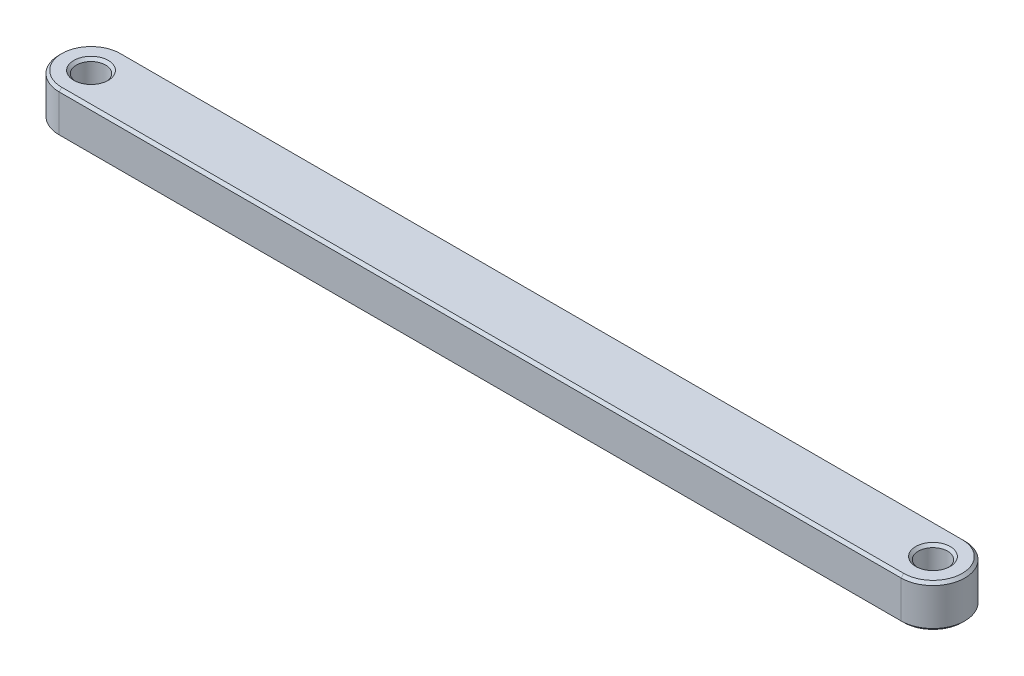
SolidWorks part; units mm, degrees
ref_plane "Front Plane" through (0, 0, 0) normal (0, 0, 1) x (1, 0, 0)
ref_plane "Top Plane" through (0, 0, 0) normal (0, 1, 0) x (1, 0, 0)
ref_plane "Right Plane" through (0, 0, 0) normal (1, 0, 0) x (0, 0, -1)
sketch "Sketch1" plane through (0, 0, 0) normal (0, 1, 0) x (1, 0, 0)
  line L0 (0, 0) -> (125.7224, 0) construction
  line L1 (0, 4.7625) -> (125.7224, 4.7625)
  line L2 (0, -4.7625) -> (125.7224, -4.7625)
  arc A0 (0, 4.7625) -> (0, -4.7625) centre (0, 0) ccw
  arc A1 (125.7224, -4.7625) -> (125.7224, 4.7625) centre (125.7224, 0) ccw
  circle A2 centre (0, 0) radius 2.1828
  circle A3 centre (125.7224, 0) radius 2.1828
  point P3 (62.8612, 0)
  dimension "D2" = 4.7625
  dimension "D3" = 4.3656
  dimension "D4" = 4.3656
  dimension "D1" = 125.7224
extrude "Boss-Extrude1" add sketch "Sketch1" along normal blind 6.35
chamfer "Chamfer1" distance 0.3969 angle 45 12 edges at (125.7224, 0, 2.1828) (0, 0, 2.1828) (62.8612, 0, 4.7625) (130.4849, 0, 0) (62.8612, 0, -4.7625) (-4.7625, 0, 0) (125.7224, 6.35, 2.1828) (62.8612, 6.35, -4.7625) (130.4849, 6.35, 0) (62.8612, 6.35, 4.7625) (-4.7625, 6.35, 0) (0, 6.35, 2.1828)
